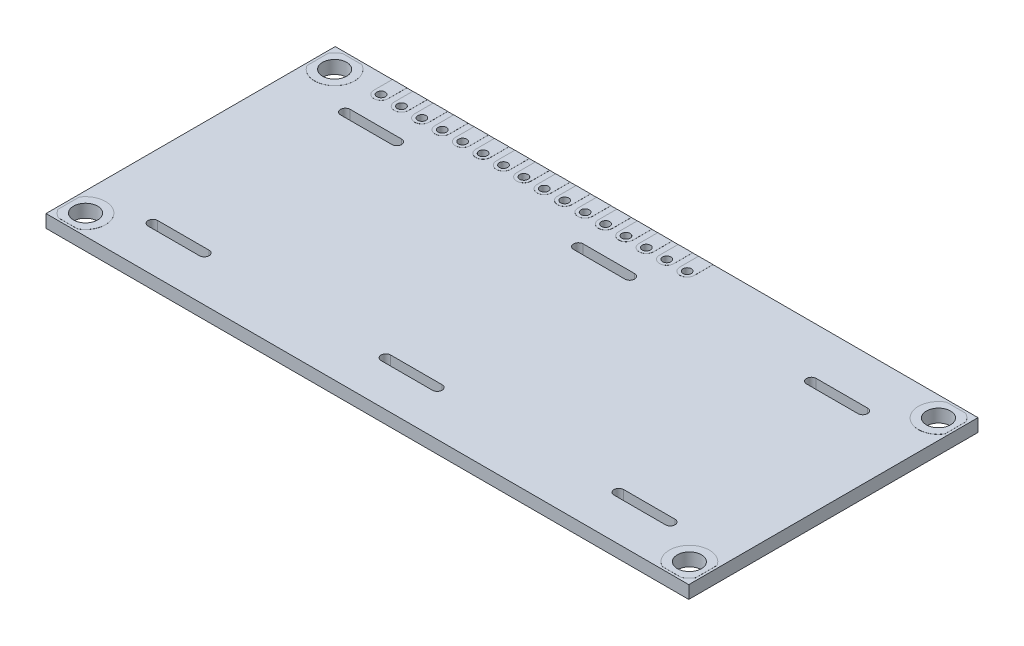
SolidWorks part; units mm, degrees
ref_plane "Plan de face" through (0, 0, 0) normal (0, 0, 1) x (1, 0, 0)
ref_plane "Plan de dessus" through (0, 0, 0) normal (0, 1, 0) x (1, 0, 0)
ref_plane "Plan de droite" through (0, 0, 0) normal (1, 0, 0) x (0, 0, -1)
sketch "Esquisse1" plane through (0, 0, 0) normal (0, 1, 0) x (1, 0, 0)
  line L0 (40, 36) -> (40, 28.6716) construction
  line L1 (0, 0) -> (80, 0)
  line L2 (0, 0) -> (0, 36)
  line L3 (0, 36) -> (80, 36)
  line L4 (80, 0) -> (80, 36)
  line L5 (0, 18) -> (8.7916, 18) construction
  line L6 (-3.0961, 33.68) -> (82.0612, 33.68) construction
  line L7 (7.7, 30.16) -> (14.1, 30.16)
  line L8 (7.7, 6.2) -> (14.1, 6.2)
  line L9 (7.7, 28.96) -> (14.1, 28.96)
  line L10 (7.7, 5) -> (14.1, 5)
  line L11 (36.7, 30.16) -> (43.1, 30.16)
  line L12 (36.7, 28.96) -> (43.1, 28.96)
  line L13 (36.7, 6.2) -> (43.1, 6.2)
  line L14 (36.7, 5) -> (43.1, 5)
  line L15 (65.7, 30.16) -> (72.1, 30.16)
  line L16 (65.7, 28.96) -> (72.1, 28.96)
  line L17 (65.7, 6.2) -> (72.1, 6.2)
  line L18 (65.7, 5) -> (72.1, 5)
  line L19 (72.3, 41.4898) -> (72.3, -1.3318) construction
  circle A0 centre (2.42, 33.5) radius 1.5
  circle A1 centre (2.42, 2.5) radius 1.5
  circle A2 centre (77.58, 2.5) radius 1.5
  circle A3 centre (77.58, 33.5) radius 1.5
  circle A4 centre (8.02, 33.68) radius 0.52
  circle A5 centre (10.56, 33.68) radius 0.52
  circle A6 centre (13.1, 33.68) radius 0.52
  circle A7 centre (15.64, 33.68) radius 0.52
  circle A8 centre (18.18, 33.68) radius 0.52
  circle A9 centre (20.72, 33.68) radius 0.52
  circle A10 centre (23.26, 33.68) radius 0.52
  circle A11 centre (25.8, 33.68) radius 0.52
  circle A12 centre (28.34, 33.68) radius 0.52
  circle A13 centre (30.88, 33.68) radius 0.52
  circle A14 centre (33.42, 33.68) radius 0.52
  circle A15 centre (35.96, 33.68) radius 0.52
  circle A16 centre (38.5, 33.68) radius 0.52
  circle A17 centre (41.04, 33.68) radius 0.52
  circle A18 centre (43.58, 33.68) radius 0.52
  circle A19 centre (46.12, 33.68) radius 0.52
  arc A20 (7.7, 6.2) -> (7.7, 5) centre (7.7, 5.6) ccw
  arc A21 (14.1, 5) -> (14.1, 6.2) centre (14.1, 5.6) ccw
  arc A22 (7.7, 30.16) -> (7.7, 28.96) centre (7.7, 29.56) ccw
  arc A23 (14.1, 28.96) -> (14.1, 30.16) centre (14.1, 29.56) ccw
  arc A24 (36.7, 30.16) -> (36.7, 28.96) centre (36.7, 29.56) ccw
  arc A25 (43.1, 28.96) -> (43.1, 30.16) centre (43.1, 29.56) ccw
  arc A26 (36.7, 6.2) -> (36.7, 5) centre (36.7, 5.6) ccw
  arc A27 (43.1, 5) -> (43.1, 6.2) centre (43.1, 5.6) ccw
  arc A28 (65.7, 30.16) -> (65.7, 28.96) centre (65.7, 29.56) ccw
  arc A29 (72.1, 28.96) -> (72.1, 30.16) centre (72.1, 29.56) ccw
  arc A30 (65.7, 6.2) -> (65.7, 5) centre (65.7, 5.6) ccw
  arc A31 (72.1, 5) -> (72.1, 6.2) centre (72.1, 5.6) ccw
  dimension "D3" = 3
  dimension "D8" = 1.04
  dimension "D10" = 1.2
  dimension "D16" = 0.6
  dimension "D1" = 80
  dimension "D2" = 36
  dimension "D4" = 31
  dimension "D5" = 75.16
  dimension "D6" = 2.32
  dimension "D7" = 8.02
  dimension "D11" = 6.4
  dimension "D12" = 5
  dimension "D13" = 7.7
  dimension "D14" = 5.84
  dimension "D15" = 7.7
  dimension "D17" = 3
  dimension "D9" = 16
extrude "Boss.-Extru.1" add sketch "Esquisse1" along normal blind 1.6
sketch "Esquisse2" plane through (0, 1.6, 0) normal (0, 1, 0) x (1, 0, 0)
  line L0 (80, 36) -> (0, 36) construction
  line L1 (0.3, 32.175) -> (0.3, 34.825)
  line L2 (7.12, 33.68) -> (7.12, 36)
  line L3 (7.12, 36) -> (8.92, 36)
  line L4 (8.92, 33.68) -> (8.92, 36)
  line L5 (3.6074, 0.3) -> (1.2326, 0.3)
  line L6 (0.3, 1.175) -> (0.3, 3.825)
  line L7 (0, 36) -> (0, 0) construction
  line L8 (0, 0) -> (80, 0) construction
  line L9 (1.2326, 35.7) -> (3.6074, 35.7)
  line L10 (76.3926, 0.3) -> (78.7674, 0.3)
  line L11 (79.7, 1.175) -> (79.7, 3.825)
  line L12 (80, 0) -> (80, 36) construction
  line L13 (79.7, 32.175) -> (79.7, 34.825)
  line L14 (78.7674, 35.7) -> (76.3926, 35.7)
  line L15 (9.66, 33.68) -> (9.66, 36)
  line L16 (9.66, 36) -> (11.46, 36)
  line L17 (11.46, 33.68) -> (11.46, 36)
  line L18 (12.2, 33.68) -> (12.2, 36)
  line L19 (12.2, 36) -> (14, 36)
  line L20 (14, 33.68) -> (14, 36)
  line L21 (14.74, 33.68) -> (14.74, 36)
  line L22 (14.74, 36) -> (16.54, 36)
  line L23 (16.54, 33.68) -> (16.54, 36)
  line L24 (17.28, 33.68) -> (17.28, 36)
  line L25 (17.28, 36) -> (19.08, 36)
  line L26 (19.08, 33.68) -> (19.08, 36)
  line L27 (19.82, 33.68) -> (19.82, 36)
  line L28 (19.82, 36) -> (21.62, 36)
  line L29 (21.62, 33.68) -> (21.62, 36)
  line L30 (22.36, 33.68) -> (22.36, 36)
  line L31 (22.36, 36) -> (24.16, 36)
  line L32 (24.16, 33.68) -> (24.16, 36)
  line L33 (24.9, 33.68) -> (24.9, 36)
  line L34 (24.9, 36) -> (26.7, 36)
  line L35 (26.7, 33.68) -> (26.7, 36)
  line L36 (27.44, 33.68) -> (27.44, 36)
  line L37 (27.44, 36) -> (29.24, 36)
  line L38 (29.24, 33.68) -> (29.24, 36)
  line L39 (29.98, 33.68) -> (29.98, 36)
  line L40 (29.98, 36) -> (31.78, 36)
  line L41 (31.78, 33.68) -> (31.78, 36)
  line L42 (32.52, 33.68) -> (32.52, 36)
  line L43 (32.52, 36) -> (34.32, 36)
  line L44 (34.32, 33.68) -> (34.32, 36)
  line L45 (35.06, 33.68) -> (35.06, 36)
  line L46 (35.06, 36) -> (36.86, 36)
  line L47 (36.86, 33.68) -> (36.86, 36)
  line L48 (37.6, 33.68) -> (37.6, 36)
  line L49 (37.6, 36) -> (39.4, 36)
  line L50 (39.4, 33.68) -> (39.4, 36)
  line L51 (40.14, 33.68) -> (40.14, 36)
  line L52 (40.14, 36) -> (41.94, 36)
  line L53 (41.94, 33.68) -> (41.94, 36)
  line L54 (42.68, 33.68) -> (42.68, 36)
  line L55 (42.68, 36) -> (44.48, 36)
  line L56 (44.48, 33.68) -> (44.48, 36)
  line L57 (45.22, 33.68) -> (45.22, 36)
  line L58 (45.22, 36) -> (47.02, 36)
  line L59 (47.02, 33.68) -> (47.02, 36)
  arc A0 (3.6074, 0.3) -> (0.3, 3.825) centre (2.42, 2.5) ccw
  arc A1 (0.3, 32.175) -> (3.6074, 35.7) centre (2.42, 33.5) ccw
  arc A2 (76.3926, 35.7) -> (79.7, 32.175) centre (77.58, 33.5) ccw
  arc A3 (78.7674, 0.3) -> (79.7, 1.175) centre (77.58, 2.5) ccw
  arc A4 (7.12, 33.68) -> (8.92, 33.68) centre (8.02, 33.68) ccw
  circle A5 centre (8.02, 33.68) radius 0.52
  arc A6 (1.2326, 35.7) -> (0.3, 34.825) centre (2.42, 33.5) ccw
  arc A7 (0.3, 1.175) -> (1.2326, 0.3) centre (2.42, 2.5) ccw
  arc A8 (79.7, 3.825) -> (76.3926, 0.3) centre (77.58, 2.5) ccw
  arc A9 (79.7, 34.825) -> (78.7674, 35.7) centre (77.58, 33.5) ccw
  arc A10 (9.66, 33.68) -> (11.46, 33.68) centre (10.56, 33.68) ccw
  circle A11 centre (10.56, 33.68) radius 0.52
  arc A12 (12.2, 33.68) -> (14, 33.68) centre (13.1, 33.68) ccw
  circle A13 centre (13.1, 33.68) radius 0.52
  arc A14 (14.74, 33.68) -> (16.54, 33.68) centre (15.64, 33.68) ccw
  circle A15 centre (15.64, 33.68) radius 0.52
  arc A16 (17.28, 33.68) -> (19.08, 33.68) centre (18.18, 33.68) ccw
  circle A17 centre (18.18, 33.68) radius 0.52
  arc A18 (19.82, 33.68) -> (21.62, 33.68) centre (20.72, 33.68) ccw
  circle A19 centre (20.72, 33.68) radius 0.52
  arc A20 (22.36, 33.68) -> (24.16, 33.68) centre (23.26, 33.68) ccw
  circle A21 centre (23.26, 33.68) radius 0.52
  arc A22 (24.9, 33.68) -> (26.7, 33.68) centre (25.8, 33.68) ccw
  circle A23 centre (25.8, 33.68) radius 0.52
  arc A24 (27.44, 33.68) -> (29.24, 33.68) centre (28.34, 33.68) ccw
  circle A25 centre (28.34, 33.68) radius 0.52
  arc A26 (29.98, 33.68) -> (31.78, 33.68) centre (30.88, 33.68) ccw
  circle A27 centre (30.88, 33.68) radius 0.52
  arc A28 (32.52, 33.68) -> (34.32, 33.68) centre (33.42, 33.68) ccw
  circle A29 centre (33.42, 33.68) radius 0.52
  arc A30 (35.06, 33.68) -> (36.86, 33.68) centre (35.96, 33.68) ccw
  circle A31 centre (35.96, 33.68) radius 0.52
  arc A32 (37.6, 33.68) -> (39.4, 33.68) centre (38.5, 33.68) ccw
  circle A33 centre (38.5, 33.68) radius 0.52
  arc A34 (40.14, 33.68) -> (41.94, 33.68) centre (41.04, 33.68) ccw
  circle A35 centre (41.04, 33.68) radius 0.52
  arc A36 (42.68, 33.68) -> (44.48, 33.68) centre (43.58, 33.68) ccw
  circle A37 centre (43.58, 33.68) radius 0.52
  arc A38 (45.22, 33.68) -> (47.02, 33.68) centre (46.12, 33.68) ccw
  circle A39 centre (46.12, 33.68) radius 0.52
  circle A40 centre (2.42, 33.5) radius 1.5
  circle A41 centre (2.42, 2.5) radius 1.5
  circle A42 centre (77.58, 2.5) radius 1.5
  circle A43 centre (77.58, 33.5) radius 1.5
  dimension "D1" = 1.8
  dimension "D2" = 5
  dimension "D5" = 5
  dimension "D8" = 5
  dimension "D11" = 5
  dimension "D3" = 0.3
  dimension "D4" = 0.3
  dimension "D6" = 0.3
  dimension "D7" = 0.3
  dimension "D9" = 0.3
  dimension "D10" = 0.3
  dimension "D12" = 0.3
  dimension "D13" = 0.3
  dimension "D14" = 16
extrude "Boss.-Extru.2" add sketch "Esquisse2" along normal blind 0.01
extrude "Boss.-Extru.3" add sketch "Esquisse2<2>" against normal blind 0.01 from surface starting at face at (68.9, 0, -5.6)
sketch "Esquisse2<2>" plane through (0, 1.6, 0) normal (0, 1, 0) x (1, 0, 0) same geometry as "Esquisse2"
ref_plane "Plan1" through (0, 0, -18) normal (0, 0, -1) x (-1, 0, 0)
sketch "Esquisse3" plane through (0, 0, -18) normal (0, 0, -1) x (-1, 0, 0)
  line L0 (-27.5, 0) -> (-27.5, -12.0338) construction
  line L1 (-27.5, -12.0338) -> (-54, -12.0338) construction
  line L2 (-54, -12.0338) -> (-54, 0) construction
  line L3 (-37.6, 0) -> (-36.86, 0) construction
  line L4 (0, 1.6) -> (0, 0) construction
  line L5 (-62.9183, -1.2) -> (-16.9793, -1.2) construction
  line L6 (-80, 0) -> (-47.02, 0) construction
  line L7 (-67.9847, 0) -> (-4.6388, 0) construction
  line L8 (-59.75, 8.5335) -> (-59.75, -8.5682) construction
  line L9 (-20.75, 7.9666) -> (-20.75, -6.8674) construction
  line L10 (-48.25, 8.5335) -> (-48.25, -15.2765) construction
  line L11 (-34.25, 7.9666) -> (-34.25, -8.5682) construction
  line L12 (-20.75, 0) -> (-27.5, 0)
  line L13 (-27.5, 0) -> (-27.5, -1.2)
  line L14 (-54, 0) -> (-54, -1.2)
  line L15 (-54, 0) -> (-48.25, 0)
  arc A0 (-59.79, 0) -> (-59.75, -0.0173) centre (-54.02, 13.272) ccw
  arc A1 (-27.5, -1.2) -> (-20.75, 0) centre (-27.5, 18.3844) ccw
  arc A2 (-54, -1.2) -> (-48.25, 0) centre (-54.02, 13.272) ccw
  point P2 (0, 0.8)
  point P24 (-59.75, -0.0173)
  point P25 (-48.25, 0)
  point P26 (-54, -1.2)
  point P29 (-34.25, 0)
  point P30 (-20.75, 0)
  point P31 (-27.5, -1.2)
  dimension "D1" = 26.5
  dimension "D2" = 27.5
  dimension "D3" = 1.2
  dimension "D4" = 5.75
  dimension "D5" = 5.75
  dimension "D6" = 6.75
  dimension "D7" = 6.75
revolve "Révolution1" add sketch "Esquisse3" angle 360 about L2 region at (51.8325, -0.4811, -18)
revolve "Révolution2" add sketch "Esquisse3<6>" angle 360 about L0 region at (24.9581, -0.4813, -18)
sketch "Esquisse3<6>" plane through (0, 0, -18) normal (0, 0, -1) x (-1, 0, 0) same geometry as "Esquisse3"
